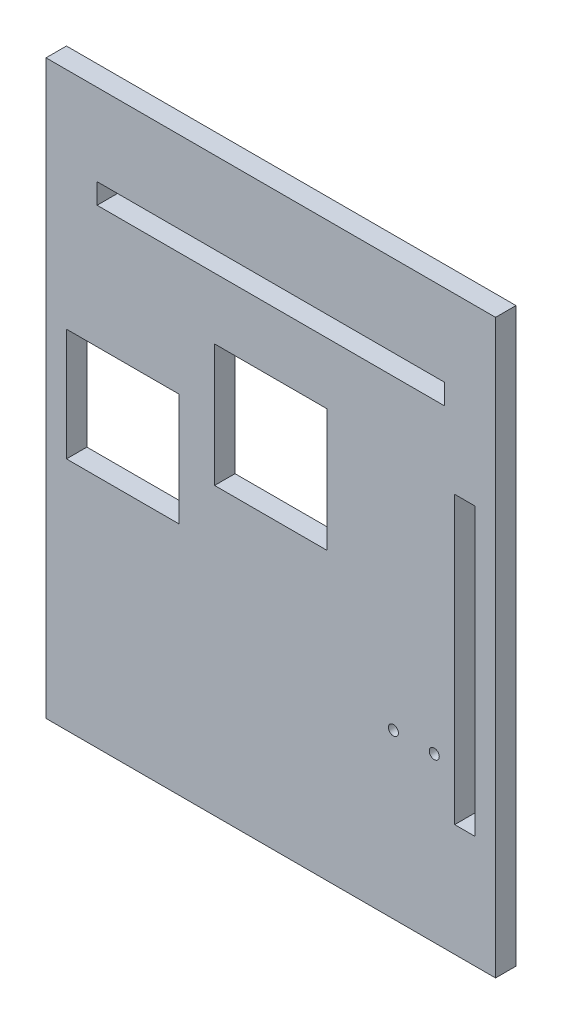
SolidWorks part; units mm, degrees
ref_plane "Front" through (0, 0, 0) normal (0, 0, 1) x (1, 0, 0)
ref_plane "Top" through (0, 0, 0) normal (0, 1, 0) x (1, 0, 0)
ref_plane "Right" through (0, 0, 0) normal (1, 0, 0) x (0, 0, -1)
sketch "Esquisse1" plane through (0, 0, 0) normal (0, 0, 1) x (1, 0, 0)
  line L1 (0, 0) -> (220, 0)
  line L2 (0, 0) -> (0, 280)
  line L3 (0, 280) -> (220, 280)
  line L4 (220, 0) -> (220, 280)
  dimension "D1" = 220
  dimension "D2" = 280
extrude "Boss.-Extru.1" add sketch "Esquisse1" along normal blind 10
sketch "Esquisse2" plane through (0, 0, 0) normal (0, -1, 0) x (1, 0, 0)
  line L0 (0, 5) -> (220, 5) construction
  line L1 (0, 10) -> (0, 0) construction
  line L2 (220, 10) -> (220, 0) construction
  line L3 (110, 5) -> (110, 28.0559) construction
  circle A0 centre (110, 5) radius 2
  circle A1 centre (210, 5) radius 2
  circle A2 centre (10, 5) radius 2
  dimension "D1" = 4
  dimension "D2" = 100
extrude "Enlèv. mat.-Extru.1" cut sketch "Esquisse2" against normal blind 10
sketch "Esquisse3" plane through (0, 0, 10) normal (0, 0, 1) x (1, 0, 0)
  line L0 (110, 0) -> (110, 280) construction
  line L1 (0, 0) -> (220, 0) construction
  line L2 (220, 280) -> (0, 280) construction
  line L3 (82.5, 200) -> (137.5, 200)
  line L4 (137.5, 200) -> (137.5, 140)
  line L5 (137.5, 140) -> (82.5, 140)
  line L6 (82.5, 200) -> (82.5, 140)
  line L8 (10, 170) -> (65, 170)
  line L9 (10, 170) -> (10, 115)
  line L10 (10, 115) -> (65, 115)
  line L11 (65, 170) -> (65, 115)
  line L12 (200, 55) -> (210, 55)
  line L13 (200, 55) -> (200, 195)
  line L14 (200, 195) -> (210, 195)
  line L15 (210, 55) -> (210, 195)
  point P11 (110, 140)
  point P12 (110, 200)
  dimension "D1" = 60
  dimension "D2" = 55
  dimension "D3" = 140
  dimension "D4" = 55
  dimension "D5" = 45
  dimension "D6" = 55
  dimension "D7" = 115
  dimension "D8" = 140
  dimension "D9" = 55
  dimension "D10" = 90
  dimension "D11" = 10
extrude "Enlèv. mat.-Extru.2" cut sketch "Esquisse3" against normal through all both and the other way through all
sketch "Esquisse5" plane through (0, 0, 10) normal (0, 0, 1) x (1, 0, 0)
  line L0 (110, 230) -> (110, 0) construction
  line L1 (25, 240) -> (195, 240)
  line L2 (25, 240) -> (25, 230)
  line L3 (25, 230) -> (195, 230)
  line L4 (195, 240) -> (195, 230)
  line L5 (0, 0) -> (220, 0) construction
  dimension "D1" = 170
  dimension "D2" = 10
  dimension "D3" = 230
extrude "Enlèv. mat.-Extru.3" cut sketch "Esquisse5" against normal through all both and the other way through all
sketch "Esquisse6" plane through (0, 0, 10) normal (0, 0, 1) x (1, 0, 0)
  line L0 (170, 80) -> (190, 80) construction
  line L1 (0, 0) -> (220, 0) construction
  line L2 (137.5, 140) -> (82.5, 140) construction
  circle A0 centre (190, 80) radius 2.45
  circle A1 centre (170, 80) radius 2.45
  point P8 (110, 140)
  dimension "D1" = 4.9
  dimension "D3" = 80
  dimension "D2" = 20
  dimension "D4" = 60
extrude "Enlèv. mat.-Extru.4" cut sketch "Esquisse6" against normal through all both and the other way through all
